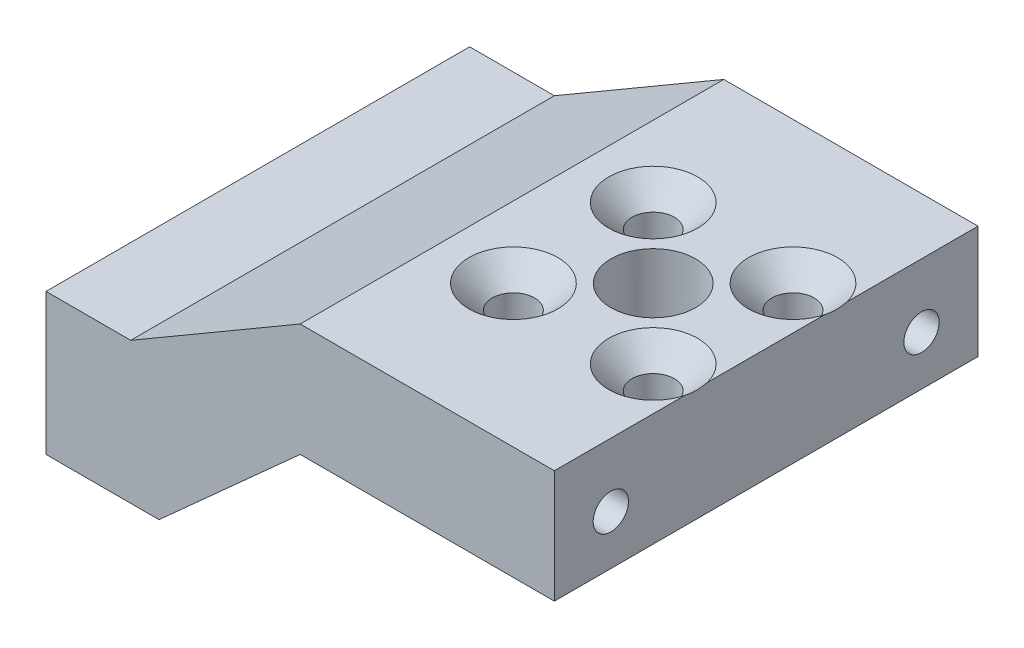
SolidWorks part; units mm, degrees
ref_plane "Спереди" through (0, 0, 0) normal (0, 0, 1) x (1, 0, 0)
ref_plane "Сверху" through (0, 0, 0) normal (0, 1, 0) x (1, 0, 0)
ref_plane "Справа" through (0, 0, 0) normal (1, 0, 0) x (0, 0, -1)
sketch "Эскиз1" plane through (0, 0, 0) normal (0, 1, 0) x (1, 0, 0)
  line L1 (0, 0) -> (41, 0)
  line L2 (0, 0) -> (0, 30)
  line L3 (0, 30) -> (41, 30)
  line L4 (41, 0) -> (41, 30)
  dimension "D1" = 41
  dimension "D2" = 30
extrude "Бобышка-Вытянуть1" add sketch "Эскиз1" along normal blind 10
sketch "Эскиз3" plane through (0, 0, 0) normal (-1, 0, 0) x (0, 0, 1)
  line L0 (-30, 10) -> (0, 10) construction
  line L1 (-30, 10) -> (0, 10)
  line L2 (-30, 10) -> (-30, 0)
  line L3 (-30, 0) -> (0, 0)
  line L4 (0, 10) -> (0, 0)
  line L5 (-30, 0) -> (0, 0) construction
  point P6 (-15, 10)
  point P9 (-15, 0)
  dimension "D1" = 10
  dimension "D2" = 30
extrude "Вырез-Вытянуть2" cut sketch "Эскиз3" against normal blind 3
sketch "Эскиз4" plane through (3, 0, 0) normal (-1, 0, 0) x (0, 0, 1)
  line L0 (-20, 5.4) -> (-8.75, 5.4) construction
  line L1 (0, 10) -> (-30, 10) construction
  line L2 (-20, 4.15) -> (-10, 4.15) construction
  circle A0 centre (-20, 5.4) radius 1.25
  circle A1 centre (-10, 5.4) radius 1.25
  text T0 "отверстия под 2,9 * 9.5  саморез" font "Arial" height 2
  point P5 (-15, 10)
  dimension "D1" = 5
  dimension "D2" = 2.5
  dimension "D3" = 10
  dimension "D4" = 4.6
extrude "Вырез-Вытянуть3" cut sketch "Эскиз4" against normal blind 5
sketch "Эскиз7" plane through (0, 0, -30) normal (0, 0, -1) x (-1, 0, 0)
  line L0 (-39, 10) -> (-39, 17) construction
  line L1 (-39, 17) -> (-21, 17)
  line L2 (-21, 17) -> (-9, 10)
  line L3 (-41, 10) -> (-3, 10) construction
  line L4 (-39, 10) -> (-9, 10)
  line L5 (-39, 17) -> (-39, 10)
  line L6 (-3, 10) -> (-3, 0) construction
  dimension "D1" = 12
  dimension "D2" = 18
  dimension "D3" = 18
  dimension "D4" = 7
extrude "Бобышка-Вытянуть3" add sketch "Эскиз7" against normal blind 30
sketch "Эскиз6" plane through (0, 0, 0) normal (0, -1, 0) x (1, 0, 0)
  line L0 (3, 0) -> (41, 0) construction
  line L1 (41, -30) -> (21, -30)
  line L2 (41, -30) -> (41, 0)
  line L3 (41, 0) -> (21, 0)
  line L4 (21, -30) -> (21, 0)
  dimension "D1" = 20
extrude "Вырез-Вытянуть5" cut sketch "Эскиз6" against normal blind 9
sketch "Эскиз2" plane through (39, 0, 0) normal (1, 0, 0) x (0, 0, -1)
  line L0 (0, 12.5) -> (30, 12.5) construction
  line L1 (0, 17) -> (30, 17) construction
  line L2 (0, 17) -> (0, 10) construction
  circle A0 centre (4, 12.5) radius 1.25
  circle A1 centre (26, 12.5) radius 1.25
  dimension "D1" = 2.5
  dimension "D2" = 2.5
  dimension "D3" = 4.5
  dimension "D4" = 22
  dimension "D5" = 4
extrude "Вырез-Вытянуть1" cut sketch "Эскиз2" against normal blind 4.5
sketch "Эскиз8" plane through (0, 9, 0) normal (0, 1, 0) x (1, 0, 0)
  line L0 (31, 15) -> (37.0104, 21.0104) construction
  line L1 (31, 15) -> (24.9896, 8.9896) construction
  line L2 (21, 0) -> (39, 0) construction
  line L3 (31, 15) -> (42.7004, 15) construction
  line L4 (24.9896, 21.0104) -> (37.0104, 8.9896) construction
  line L6 (21, 0) -> (21, 30) construction
  circle A0 centre (31, 15) radius 7 construction
  circle A1 centre (31, 15) radius 8.5 construction
  circle A2 centre (35.9497, 19.9497) radius 1.5
  circle A3 centre (35.9497, 10.0503) radius 1.5
  circle A4 centre (26.0503, 10.0503) radius 1.5
  circle A5 centre (26.0503, 19.9497) radius 1.5
  point P20 (31, 15)
  dimension "D1" = 14
  dimension "D2" = 17
  dimension "D6" = 4
  dimension "D3" = 10
  dimension "D4" = 15
  dimension "D5" = 45
extrude "Вырез-Вытянуть6" cut sketch "Эскиз8" along normal through all
sketch "Эскиз9" plane through (0, 0, -30) normal (0, 0, -1) x (-1, 0, 0)
  line L0 (-21, 9) -> (-21, 0)
  line L1 (-21, 9) -> (-21, 0) construction
  line L2 (-21, 0) -> (-11, 0)
  line L3 (-21, 0) -> (-3, 0) construction
  line L4 (-11, 0) -> (-21, 9)
  dimension "D1" = 10
extrude "Вырез-Вытянуть7" cut sketch "Эскиз9" against normal through all
sketch "Эскиз11" plane through (0, 0, -30) normal (0, 0, -1) x (-1, 0, 0)
  line L1 (-39, 10) -> (-43.132, 10)
  line L2 (-39, 10) -> (-39, 6.7442)
  line L3 (-39, 6.7442) -> (-43.132, 6.7442)
  line L4 (-43.132, 10) -> (-43.132, 6.7442)
extrude "Вырез-Вытянуть9" cut sketch "Эскиз11" against normal through all
chamfer "Chamfer1" distance 1.65 angle 45 4 edges at (35.9497, 17, -18.4497) (26.0503, 17, -18.4497) (26.0503, 17, -8.5503) (35.9497, 17, -8.5503)
sketch "Sketch1" plane through (0, 17, 0) normal (0, 1, 0) x (1, 0, 0)
  circle A0 centre (31, 15) radius 3
  circle A1 centre (26.0503, 10.0503) radius 1.5 construction
  circle A3 centre (26.0503, 19.9497) radius 1.5 construction
  dimension "D1" = 6
  dimension "D2" = 7
  dimension "D3" = 7
extrude "Extrude1" cut sketch "Sketch1" against normal through all
